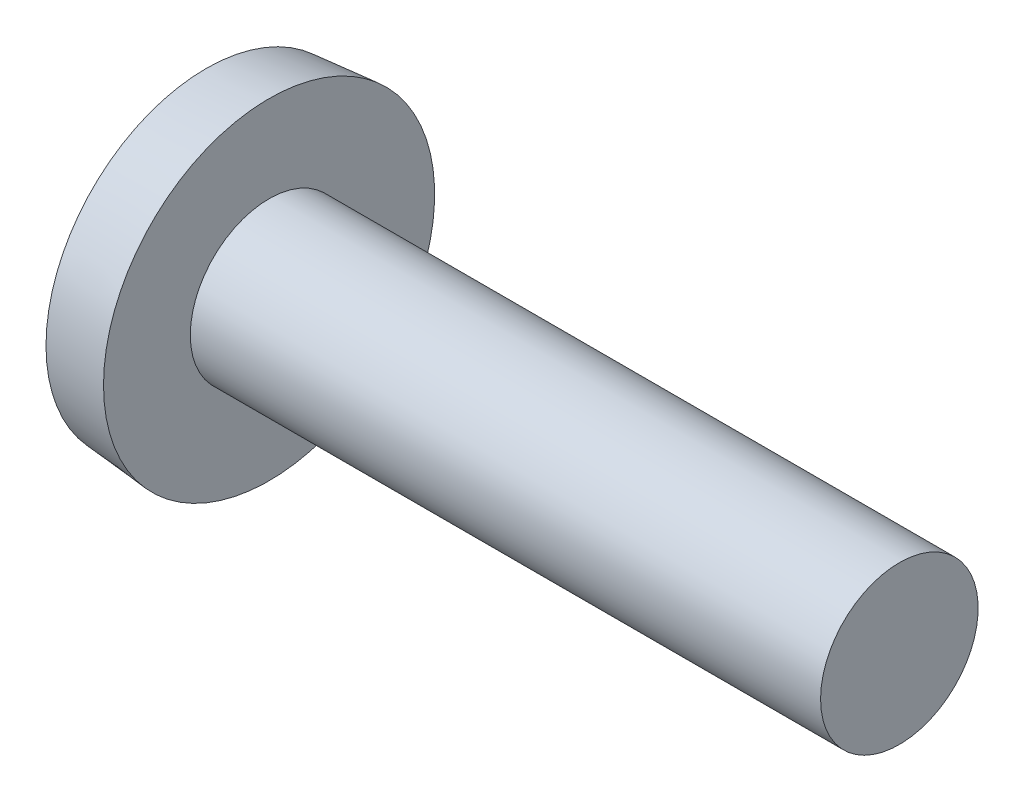
SolidWorks part; units mm, degrees
material "Stainless Steel (ferritic)"
ref_plane "Plane1" through (0, 0, 0) normal (0, 0, 1) x (1, 0, 0)
ref_plane "Plane2" through (0, 0, 0) normal (0, 1, 0) x (1, 0, 0)
ref_plane "Plane3" through (0, 0, 0) normal (1, 0, 0) x (0, 0, -1)
sketch "BodySke" plane through (0, 0, 0) normal (0, 0, 1) x (1, 0, 0)
  line L0 (6.1976, 4.7625) -> (6.1976, 10.0076)
  line L1 (6.1976, 10.0076) -> (2.3876, 9.6743)
  line L2 (-25.4, 0) -> (127, 0) construction
  line L3 (6.1976, -10.0076) -> (2.3876, -9.6743) construction
  line L4 (6.1976, 4.7625) -> (44.2976, 4.7625)
  line L5 (44.2976, 4.7625) -> (44.2976, 0)
  line L6 (44.2976, 0) -> (0, 0)
  line L7 (6.1976, -4.7625) -> (44.2976, -4.7625) construction
  line L8 (7.2568, 6.35) -> (7.2568, -3.175) construction
  line L9 (37.9476, 6.35) -> (37.9476, -3.175) construction
  arc A0 (0, 0) -> (2.3876, 9.6743) centre (20.7933, 0) cw
  dimension "Diameter" = 9.525
revolve "Base-Revolve" add sketch "BodySke" angle 360 about L2
cosmetic thread "ThreadCosmetic" [suppressed] parameters "Thread_length"=6.35, "Thread_minor"=4.2266
sketch "Sketch2" plane through (0, 0, 0) normal (1, 0, 0) x (0, 0, -1)
  line L0 (10.0076, -0.8509) -> (10.0076, 0.8509)
  line L1 (10.0076, 0.8509) -> (-10.0076, 0.8509)
  line L2 (-10.0076, 0.8509) -> (-10.0076, -0.8509)
  line L3 (-10.0076, -0.8509) -> (10.0076, -0.8509)
  dimension "D1" = 20.0152
  dimension "D2" = 10.0076
  dimension "D3" = 0.8509
extrude "Slot" cut sketch "Sketch2" along normal blind 2.2606
sketch "Sketch3" plane through (0, 0, 0) normal (1, 0, 0) x (0, 0, -1)
  line L0 (-1.0287, 6.096) -> (1.0287, 6.096)
  line L1 (1.0287, 6.096) -> (1.0287, -6.096)
  line L2 (1.0287, -6.096) -> (-1.0287, -6.096)
  line L3 (-1.0287, -6.096) -> (-1.0287, 6.096)
  dimension "D1" = 1.0287
  dimension "D2" = 6.096
ref_plane "Plane4" through (4.3434, 0, 0) normal (1, 0, 0) x (0, 0, -1)
sketch "Sketch4" plane through (4.3434, 0, 0) normal (1, 0, 0) x (0, 0, -1)
  line L0 (-0.5143, 0.5143) -> (0.5143, 0.5143)
  line L1 (0.5143, 0.5143) -> (0.5144, -0.5143)
  line L2 (0.5144, -0.5143) -> (-0.5143, -0.5144)
  line L3 (-0.5143, -0.5144) -> (-0.5143, 0.5143)
  dimension "D1" = 1.0287
  dimension "D2" = 0.5143
  dimension "D3" = 1.0287
  dimension "D4" = 0.5143
loft "Cross" cut profiles "Sketch3", "Sketch4"
pattern_circular "CirPattern1" count 2 every 90 about axis through (-25.4, 0, 0) along (1, 0, 0) of "Cross"
sketch "ThdSchSke" plane through (0, 0, 0) normal (0, 0, 1) x (1, 0, 0)
  line L0 (37.9476, -2.1133) -> (36.0926, -4.7625)
  line L1 (37.9476, -2.1133) -> (39.8026, -4.7625)
  line L2 (39.8026, -4.7625) -> (39.8026, -5.9531)
  line L3 (-3.175, 0) -> (5.1513, 0) construction
  line L5 (39.8026, -5.9531) -> (36.0926, -5.9531)
  line L6 (36.0926, -5.9531) -> (36.0926, -4.7625)
  dimension "Thread_minor" = 4.2266
  dimension "Diameter" = 9.525
  dimension "Start" = 37.9476
revolve "ThreadSchematic" [suppressed] cut sketch "ThdSchSke" angle 360 about L3
pattern_linear "ThdSchPat" [suppressed]
equation "\"D1@Sketch3\" = \"Cross_width@Sketch3\" / 2"
equation "\"D2@Sketch3\" = \"Cross_dia@Sketch3\" / 2"
equation "\"D1@Sketch4\" = \"Cross_width@Sketch3\"*.5"
equation "\"D2@Sketch4\" = \"D1@Sketch4\" / 2"
equation "\"D3@Sketch4\" = \"D1@Sketch4\""
equation "\"D4@Sketch4\" = \"D2@Sketch4\""
equation "\"D1@Sketch2\" = \"Head_dia@BodySke\""
equation "\"D2@Sketch2\" = \"D1@Sketch2\" / 2"
equation "\"D3@Sketch2\" = \"Slot_width@Sketch2\" / 2"
equation "\"Thread_length@ThreadCosmetic\" = ((sgn( (\"Length@BodySke\" - \"Advance@BodySke\" ) - \"Thread_nom@BodySke\" )-1)*( (\"Length@BodySke\" - \"Advance@BodySke\" ) - \"Thread_nom@BodySke\" ))/-2+ \"Thread_nom@BodySke\""
equation "\"Thread_minor@ThdSchSke\" = \"Thread_minor@ThreadCosmetic\""
equation "\"Diameter@ThdSchSke\" = \"Diameter@BodySke\""
equation "\"Overcut@ThdSchSke\" = \"Diameter@BodySke\" * 1.25"
equation "\"Start@ThdSchSke\" = \"Head_ht@BodySke\" + \"Length@BodySke\" - \"Thread_length@ThreadCosmetic\"  '---Non-countersunk---"
equation "\"Num_threads@ThdSchPat\" = int( \"Thread_length@ThreadCosmetic\" / \"Advance@BodySke\" + 0.999 )  + 1"
equation "\"Advance@ThdSchPat\" = \"Thread_length@ThreadCosmetic\" /  (\"Num_threads@ThdSchPat\" - 1) 'relax it"
